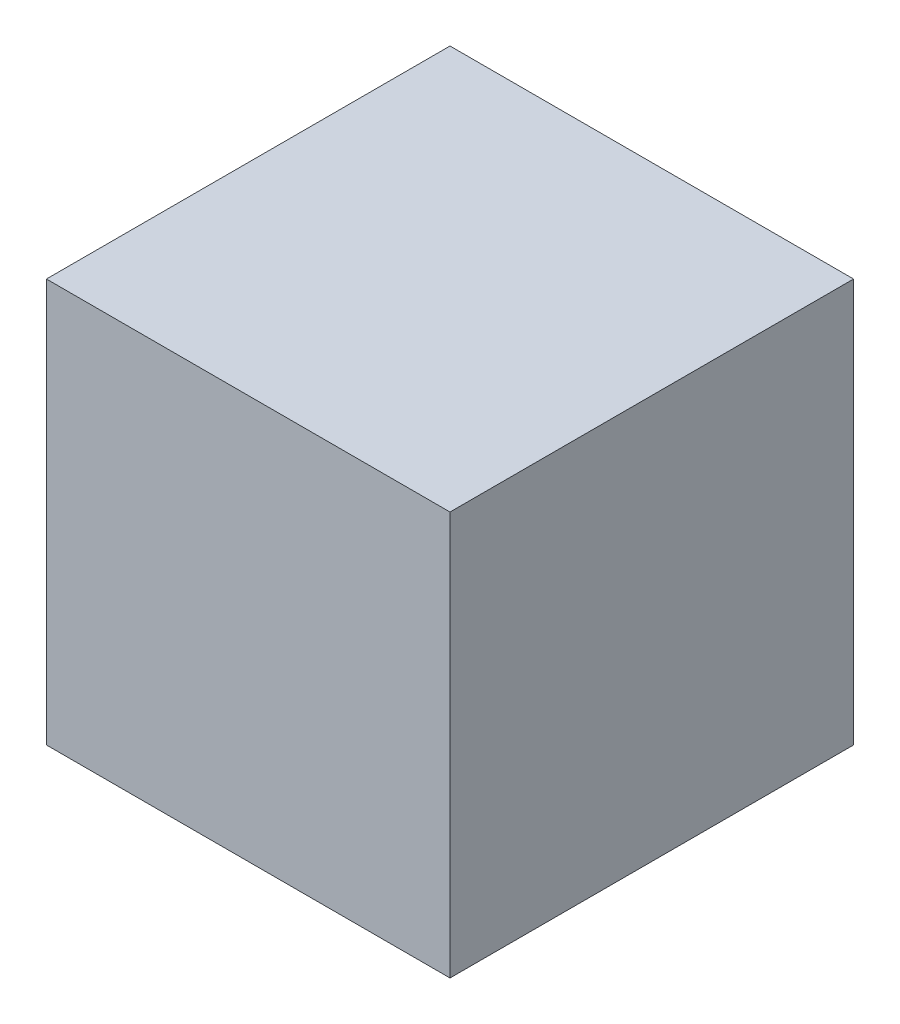
SolidWorks part; units mm, degrees
ref_plane "Front Plane" through (0, 0, 0) normal (0, 0, 1) x (1, 0, 0)
ref_plane "Top Plane" through (0, 0, 0) normal (0, 1, 0) x (1, 0, 0)
ref_plane "Right Plane" through (0, 0, 0) normal (1, 0, 0) x (0, 0, -1)
sketch "Sketch1" plane through (0, 0, 0) normal (0, 1, 0) x (1, 0, 0)
  line L1 (-4.7, -4.7) -> (4.7, -4.7)
  line L2 (-4.7, -4.7) -> (-4.7, 4.7)
  line L3 (-4.7, 4.7) -> (4.7, 4.7)
  line L4 (4.7, -4.7) -> (4.7, 4.7)
  line L5 (-4.7, -4.7) -> (4.7, 4.7) construction
  line L6 (-4.7, 4.7) -> (4.7, -4.7) construction
  point P0 (0, 0)
  dimension "D1" = 9.4
  dimension "D2" = 9.4
extrude "Boss-Extrude1" add sketch "Sketch1" along normal blind 4.7 and the other way blind 4.7
